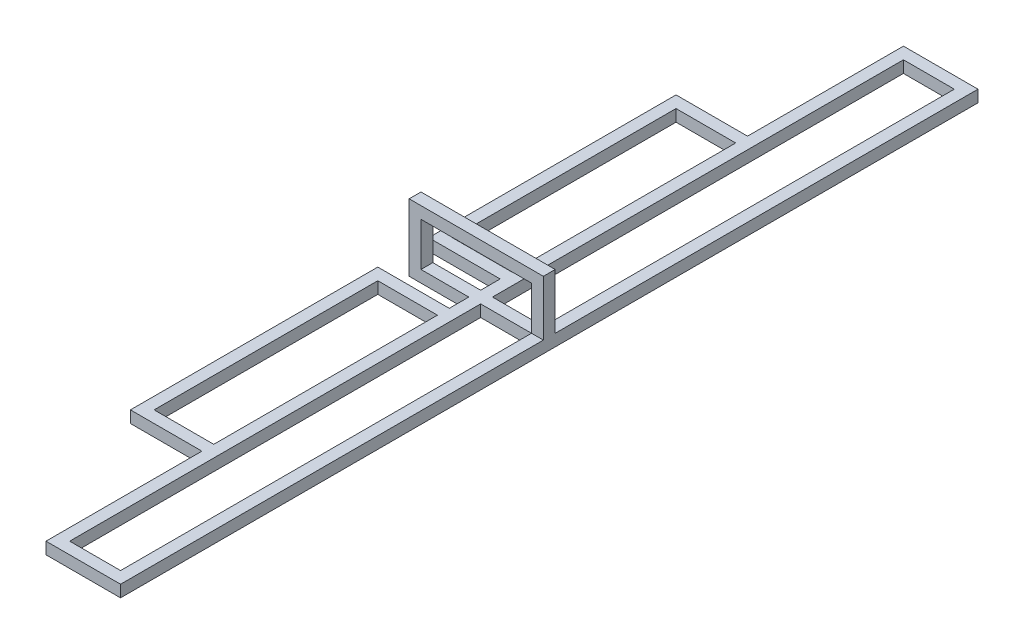
SolidWorks part; units mm, degrees
ref_plane "Front Plane" through (0, 0, 0) normal (0, 0, 1) x (1, 0, 0)
ref_plane "Top Plane" through (0, 0, 0) normal (0, 1, 0) x (1, 0, 0)
ref_plane "Right Plane" through (0, 0, 0) normal (1, 0, 0) x (0, 0, -1)
sketch "Sketch1" plane through (0, 0, 0) normal (0, 1, 0) x (1, 0, 0)
  line L1 (-50, 575) -> (50, 575)
  line L2 (-50, 575) -> (-50, -575)
  line L3 (-50, -575) -> (50, -575)
  line L4 (50, 575) -> (50, -575)
  line L8 (-34.125, 559.125) -> (34.125, 559.125)
  line L9 (34.125, 559.125) -> (34.125, -559.125)
  line L10 (-34.125, -559.125) -> (34.125, -559.125)
  line L11 (-34.125, 559.125) -> (-34.125, -559.125)
  point P4 (0, 575)
  point P6 (50, 0)
  dimension "D1" = 100
  dimension "D2" = 1150
  dimension "D3" = 15.875
extrude "Boss-Extrude1" add sketch "Sketch1" along normal blind 15.875
sketch "Sketch3" plane through (0, 15.875, 0) normal (0, 1, 0) x (1, 0, 0)
  line L0 (-50, 575) -> (-50, -575) construction
  line L1 (-50, 50) -> (-130, 50)
  line L2 (-50, 50) -> (-50, 350)
  line L3 (-50, 350) -> (-130, 350)
  line L4 (-130, 50) -> (-130, 350)
  line L5 (-130, 575) -> (-130, -575) construction
  line L6 (-34.125, 365.875) -> (-145.875, 365.875)
  line L7 (-145.875, 34.125) -> (-145.875, 365.875)
  line L8 (-34.125, 34.125) -> (-145.875, 34.125)
  line L9 (-34.125, 34.125) -> (-34.125, 365.875)
  line L10 (-8.7312, 0) -> (8.7312, 0) construction
  line L11 (-34.125, -34.125) -> (-34.125, -365.875)
  line L12 (-34.125, -34.125) -> (-145.875, -34.125)
  line L13 (-145.875, -34.125) -> (-145.875, -365.875)
  line L14 (-34.125, -365.875) -> (-145.875, -365.875)
  line L15 (-130, -50) -> (-130, -350)
  line L16 (-50, -50) -> (-50, -350)
  line L17 (-50, -50) -> (-130, -50)
  line L18 (-50, -350) -> (-130, -350)
  dimension "D1" = 350
  dimension "D2" = 50
  dimension "D3" = 15.875
extrude "Boss-Extrude2" add sketch "Sketch3" against normal blind 15.875
sketch "Sketch5" plane through (0, 0, 0) normal (0, 0, 1) x (1, 0, 0)
  line L0 (-130, 959.91) -> (-130, -15.875) construction
  line L1 (50, 0) -> (-130, 0)
  line L2 (50, 0) -> (50, 90)
  line L3 (50, 90) -> (-130, 90)
  line L4 (-130, 0) -> (-130, 90)
  line L5 (34.125, 74.125) -> (-114.125, 74.125)
  line L6 (-114.125, 15.875) -> (-114.125, 74.125)
  line L7 (34.125, 15.875) -> (-114.125, 15.875)
  line L8 (34.125, 15.875) -> (34.125, 74.125)
  point P7 (0, 0)
  point P8 (50, 0)
  dimension "D1" = 90
  dimension "D2" = 15.875
extrude "Boss-Extrude3" add sketch "Sketch5" along normal mid plane 15.875
